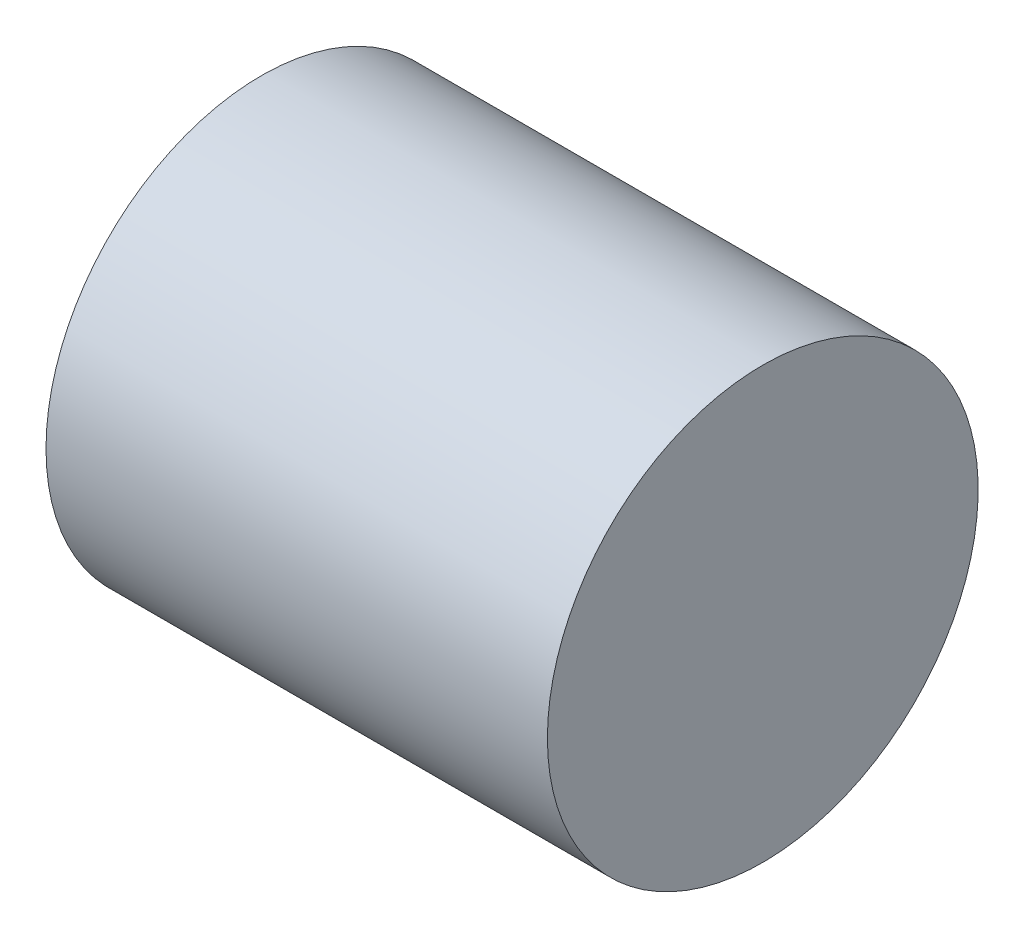
SolidWorks part; units mm, degrees
ref_plane "Front Plane" through (0, 0, 0) normal (0, 0, 1) x (1, 0, 0)
ref_plane "Top Plane" through (0, 0, 0) normal (0, 1, 0) x (1, 0, 0)
ref_plane "Right Plane" through (0, 0, 0) normal (1, 0, 0) x (0, 0, -1)
sketch "Cap_T6 Sketch" plane through (0, 0, 0) normal (0, 0, 1) x (1, 0, 0)
  line L0 (-1000, 0) -> (1000, 0) construction
  line L1 (0, 0) -> (0, 9.45)
  line L2 (0, 9.45) -> (22, 9.45)
  line L3 (22, 9.45) -> (22, 0)
  line L4 (22, 0) -> (0, 0)
revolve "Cap_T6" add sketch "Cap_T6 Sketch" angle 360 about L0
ref_axis "Engine Axis" through (23.1, 0, 0) along (-1, 0, 0)
sketch "Socket 1 Sketch" plane through (0, 0, 0) normal (0, 0, 1) x (1, 0, 0)
  line L0 (-1000, 0) -> (1000, 0) construction
  line L1 (-1, 0) -> (-1, 4.7625)
  line L2 (-1, 4.7625) -> (16.8, 4.7625)
  line L3 (16.8, 4.7625) -> (16.8, 0)
  line L4 (16.8, 0) -> (-1, 0)
revolve "Socket 1" cut sketch "Socket 1 Sketch" angle 360 about L0
